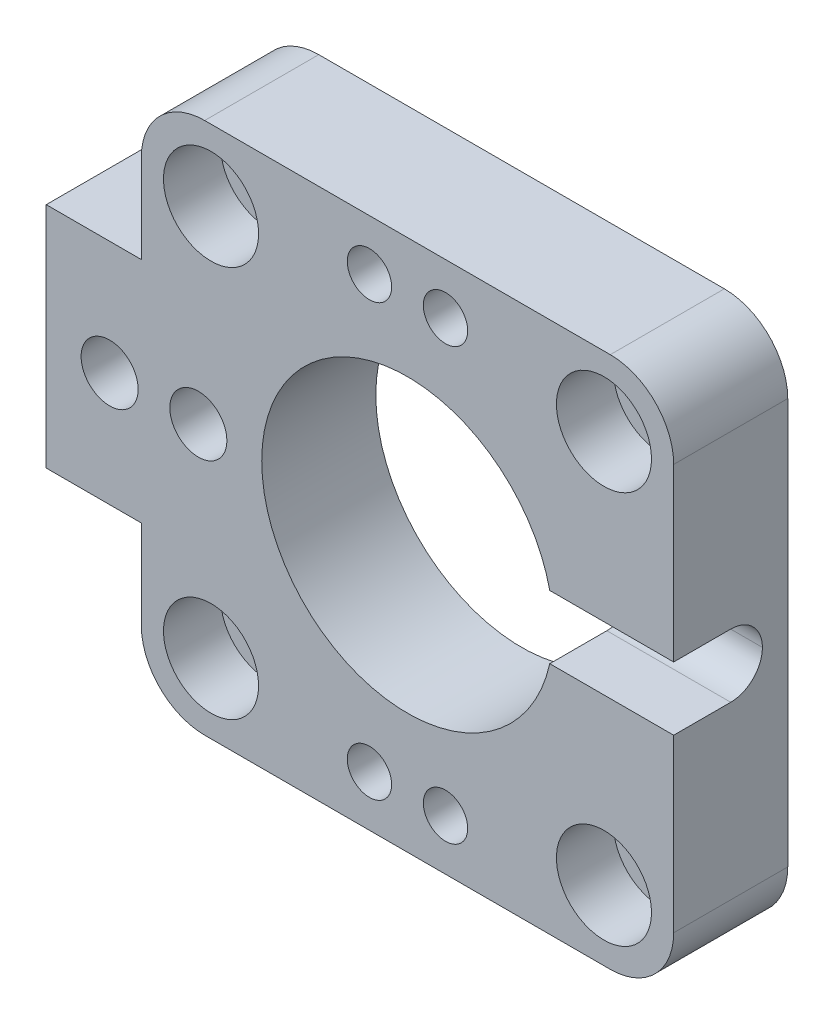
SolidWorks part; units mm, degrees
ref_plane "Plan de face" through (0, 0, 0) normal (0, 0, 1) x (1, 0, 0)
ref_plane "Plan de dessus" through (0, 0, 0) normal (0, 1, 0) x (1, 0, 0)
ref_plane "Plan de droite" through (0, 0, 0) normal (1, 0, 0) x (0, 0, -1)
sketch "Esquisse1" plane through (0, 0, 0) normal (0, 0, 1) x (1, 0, 0)
  line L1 (0, 0) -> (-42, 0)
  line L2 (0, 0) -> (0, -42)
  line L3 (0, -42) -> (-42, -42)
  line L4 (-42, 0) -> (-42, -42)
  line L5 (-42, -30) -> (-49.5, -30)
  line L6 (-42, -30) -> (-42, -12)
  line L7 (-42, -12) -> (-49.5, -12)
  line L8 (-49.5, -30) -> (-49.5, -12)
  circle A0 centre (-36.5, -5.611) radius 1.75
  circle A1 centre (-5.5, -5.5) radius 1.75
  circle A2 centre (-5.5, -36.5) radius 1.75
  circle A3 centre (-36.5, -36.5) radius 1.75
  circle A4 centre (-21, -21) radius 11.5
  dimension "D3" = 3.5
  dimension "D4" = 3.5
  dimension "D5" = 3.5
  dimension "D6" = 3.5
  dimension "D17" = 23
  dimension "D1" = 42
  dimension "D2" = 42
  dimension "D7" = 5.5
  dimension "D8" = 5.5
  dimension "D9" = 5.5
  dimension "D10" = 5.5
  dimension "D11" = 5.5
  dimension "D12" = 5.611
  dimension "D13" = 5.5
  dimension "D14" = 5.5
  dimension "D15" = 21
  dimension "D16" = 21
  dimension "D18" = 18
  dimension "D19" = 28.5
  dimension "D20" = 12
extrude "Boss.-Extru.1" add sketch "Esquisse1" along normal blind 9 contours L1 L4 L3 L2 A4 A3 A2 A1 A0 | L8 L5 L4 L7
sketch "Esquisse9" plane through (0, 0, 9) normal (0, 0, 1) x (1, 0, 0)
  line L0 (-42, -30) -> (-49.5, -30) construction
  line L1 (-49.5, -30) -> (-49.5, -12) construction
  circle A0 centre (-44.5, -21) radius 2.25
  circle A1 centre (-37.5, -21) radius 2.25
  dimension "D1" = 4.5
  dimension "D2" = 4.5
  dimension "D3" = 9
  dimension "D4" = 9
  dimension "D5" = 5
  dimension "D6" = 12
extrude "Enlèv. mat.-Extru.2" cut sketch "Esquisse9" against normal blind 17 contours A1 | A0
sketch "Esquisse10" plane through (0, 0, 0) normal (0, 0, -1) x (-1, 0, 0)
  line L0 (49.5, -30) -> (49.5, -12) construction
  line L1 (44.5, -25.3301) -> (48.25, -23.1651)
  line L2 (48.25, -23.1651) -> (48.25, -18.8349)
  line L3 (48.25, -18.8349) -> (44.5, -16.6699)
  line L4 (44.5, -16.6699) -> (40.75, -18.8349)
  line L5 (40.75, -18.8349) -> (40.75, -23.1651)
  line L6 (40.75, -23.1651) -> (44.5, -25.3301)
  line L7 (37.5, -25.3301) -> (41.25, -23.1651)
  line L8 (41.25, -23.1651) -> (41.25, -18.8349)
  line L9 (41.25, -18.8349) -> (37.5, -16.6699)
  line L10 (37.5, -16.6699) -> (33.75, -18.8349)
  line L11 (33.75, -18.8349) -> (33.75, -23.1651)
  line L12 (33.75, -23.1651) -> (37.5, -25.3301)
  circle A2 centre (44.5, -21) radius 3.75 construction
  circle A3 centre (37.5, -21) radius 3.75 construction
  dimension "D3" = 7.5
  dimension "D4" = 7.5
  dimension "D5" = 0
  dimension "D6" = 0
extrude "Enlèv. mat.-Extru.3" cut sketch "Esquisse10" against normal blind 4.5 contours L8 L9 L10 L11 L12 L7
sketch "Esquisse11" plane through (0, 0, 9) normal (0, 0, 1) x (1, 0, 0)
  circle A0 centre (-36.5, -5.611) radius 3.75
  circle A1 centre (-5.5, -5.5) radius 3.75
  circle A2 centre (-5.5, -36.5) radius 3.75
  circle A3 centre (-36.5, -36.5) radius 3.75
  dimension "D1" = 7.5
  dimension "D2" = 7.5
  dimension "D3" = 7.5
  dimension "D4" = 7.5
extrude "Enlèv. mat.-Extru.4" cut sketch "Esquisse11" against normal blind 4.5
fillet "Congé1" radius 5 4 edges at (0, 0, 4.5) (0, -42, 4.5) (-42, -42, 4.5) (-42, 0, 4.5)
sketch "Esquisse12" plane through (0, 0, 9) normal (0, 0, 1) x (1, 0, 0)
  line L1 (-5, -42) -> (-37, -42) construction
  line L2 (0, -5) -> (0, -37) construction
  line L3 (-42, -30) -> (-42, -37) construction
  line L4 (-5, 0) -> (-37, 0) construction
  circle A0 centre (-24, -38) radius 1.75
  circle A2 centre (-18, -38) radius 1.75
  circle A3 centre (-24, -4) radius 1.75
  circle A4 centre (-18, -4) radius 1.75
  dimension "D1" = 3.5
  dimension "D2" = 3.5
  dimension "D9" = 3.5
  dimension "D10" = 3.5
  dimension "D3" = 4
  dimension "D4" = 4
  dimension "D5" = 6
  dimension "D6" = 42
  dimension "D7" = 18
  dimension "D8" = 18
  dimension "D11" = 18
  dimension "D12" = 6
  dimension "D13" = 4
  dimension "D14" = 4
extrude "Enlèv. mat.-Extru.5" cut sketch "Esquisse12" against normal blind 10
sketch "Esquisse14" plane through (0, 0, 0) normal (0, 0, -1) x (-1, 0, 0)
  line L1 (27, -39.7321) -> (27, -36.2679)
  line L2 (27, -36.2679) -> (24, -34.5359)
  line L3 (24, -34.5359) -> (21, -36.2679)
  line L4 (21, -36.2679) -> (21, -39.7321)
  line L5 (21, -39.7321) -> (24, -41.4641)
  line L6 (24, -41.4641) -> (27, -39.7321)
  line L7 (21, -39.7321) -> (21, -36.2679)
  line L8 (21, -36.2679) -> (18, -34.5359)
  line L9 (18, -34.5359) -> (15, -36.2679)
  line L10 (15, -36.2679) -> (15, -39.7321)
  line L11 (15, -39.7321) -> (18, -41.4641)
  line L12 (18, -41.4641) -> (21, -39.7321)
  line L13 (27, -5.7321) -> (27, -2.2679)
  line L14 (27, -2.2679) -> (24, -0.5359)
  line L15 (24, -0.5359) -> (21, -2.2679)
  line L16 (21, -2.2679) -> (21, -5.7321)
  line L17 (21, -5.7321) -> (24, -7.4641)
  line L18 (24, -7.4641) -> (27, -5.7321)
  line L19 (21, -2.2679) -> (18, -0.5359)
  line L20 (18, -0.5359) -> (15, -2.2679)
  line L21 (15, -2.2679) -> (15, -5.7321)
  line L22 (15, -5.7321) -> (18, -7.4641)
  line L23 (18, -7.4641) -> (21, -5.7321)
  line L24 (21, -5.7321) -> (21, -2.2679)
  circle A2 centre (24, -38) radius 3 construction
  circle A6 centre (24, -4) radius 3 construction
  circle A7 centre (18, -4) radius 3 construction
  dimension "D1" = 6
  dimension "D2" = 360
  dimension "D3" = 0
  dimension "D4" = 0
  dimension "D7" = 0
  dimension "D5" = 6
  dimension "D6" = 6
  dimension "D8" = 6
extrude "Enlèv. mat.-Extru.8" cut sketch "Esquisse14" against normal blind 4.5
sketch "Esquisse15" plane through (0, 0, 0) normal (1, 0, 0) x (0, 0, -1)
  line L0 (-9, -5) -> (-9, -37) construction
  line L1 (-9, -18.5) -> (-2, -18.5)
  line L2 (-9, -18.5) -> (-9, -23.5)
  line L3 (-9, -23.5) -> (-2, -23.5)
  line L4 (-2, -18.5) -> (-2, -23.5)
  line L5 (-9, 0) -> (0, 0) construction
  line L6 (0, -42) -> (-9, -42) construction
  point P6 (-2, -21)
  dimension "D1" = 5
  dimension "D2" = 21
  dimension "D3" = 21
  dimension "D4" = 7
extrude "Enlèv. mat.-Extru.9" cut sketch "Esquisse15" against normal blind 10
fillet "Congé2" radius 2.5 2 edges at (-4.8875, -23.5, 2) (-4.8875, -18.5, 2)
